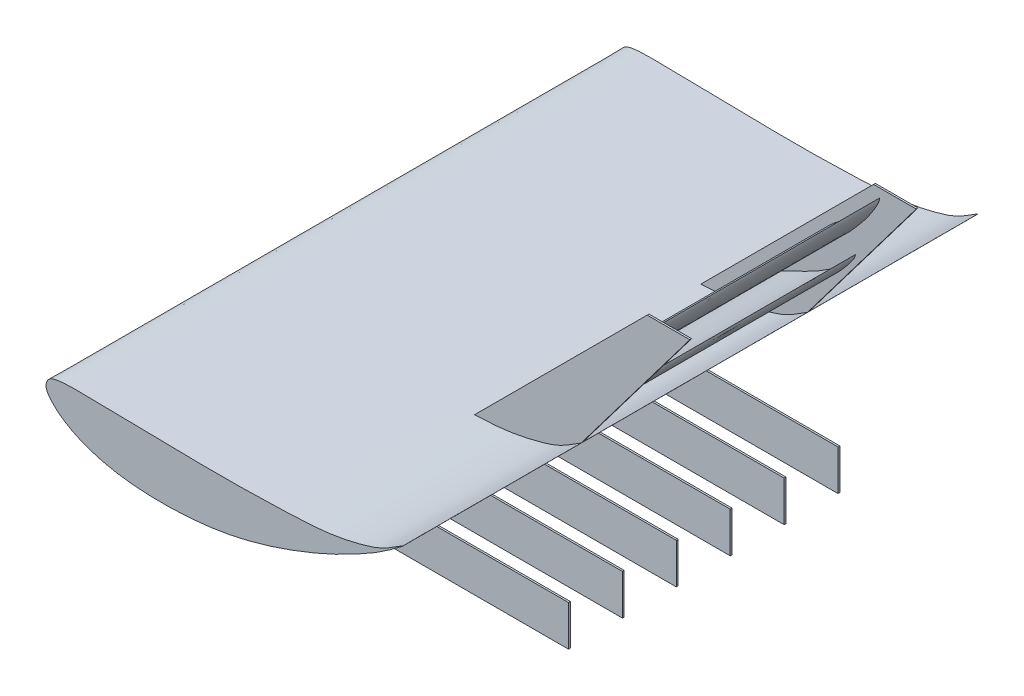
SolidWorks part; units mm, degrees
ref_plane "Front Plane" through (0, 0, 0) normal (0, 0, 1) x (1, 0, 0)
ref_plane "Top Plane" through (0, 0, 0) normal (0, 1, 0) x (1, 0, 0)
ref_plane "Right Plane" through (0, 0, 0) normal (1, 0, 0) x (0, 0, -1)
sketch "Sketch1" plane through (0, 0, 0) normal (0, 0, 1) x (1, 0, 0)
  line L0 (0, 0) -> (100, 0) construction
  line L1 (1.25, 16.6531) -> (1.25, -38.4553) construction
  line L2 (2.5, 17.9055) -> (2.5, -38.4614) construction
  line L3 (0, 16.6233) -> (0, -25.6938) construction
  line L4 (2.5, -38.4553) -> (2.5, 17.9055) construction
  line L6 (5, 17.9055) -> (5, -38.4553) construction
  line L8 (7.5, -38.4553) -> (7.5, 17.9055) construction
  line L10 (10, 17.9055) -> (10, -38.4553) construction
  line L12 (15, -38.4553) -> (15, 17.9055) construction
  line L14 (20, 17.9055) -> (20, -38.4553) construction
  line L16 (30, -38.4553) -> (30, 17.9055) construction
  line L18 (40, 17.9055) -> (40, -38.4553) construction
  line L20 (50, -38.4553) -> (50, 17.9055) construction
  line L22 (60, 17.9055) -> (60, -38.4553) construction
  line L24 (70, -38.4553) -> (70, 17.9055) construction
  line L26 (80, 17.9055) -> (80, -38.4553) construction
  line L28 (90, -38.4553) -> (90, 17.9055) construction
  line L30 (95, 17.9055) -> (95, -38.4553) construction
  line L32 (100, -38.4553) -> (100, 17.9055) construction
  spline S2 degree 3 poles (94.3673, -3.5638) (102.8561, 1.5222) (94.504, -2.988) (88.8138, -4.3065) (79.9056, -5.4947) (70.0198, -5.0741) (59.9849, -4.387) (49.9902, -3.5342) (39.9927, -2.4103) (30.0039, -1.1606) (21.6652, -0.2167) (14.9997, 0.5924) (10.0103, 1.184) (5.8366, 1.6528) (2.898, 1.5692) (0.8648, 1.1108) (-0.6238, -1.2668) (0.9385, -3.7627) (2.7533, -5.9838) (4.8768, -7.8493) (7.4255, -9.5789) (10.7358, -11.3943) (14.9019, -13.1207) (21.5668, -15.0457) (29.9416, -16.4142) (39.9918, -17.0298) (50.051, -16.6825) (60.0771, -15.2123) (70.1301, -12.7919) (80.007, -9.774) (88.8716, -6.1499) (94.3673, -3.5638) (102.8561, 1.5222) (94.504, -2.988) knots -0.105257 -0.054131 -0.027635 0 0.026268 0.051016 0.098804 0.146246 0.193788 0.241403 0.289125 0.336907 0.384666 0.408554 0.432437 0.456234 0.468112 0.474323 0.485191 0.50162 0.510955 0.52691 0.541278 0.554823 0.580548 0.60527 0.653411 0.700937 0.748406 0.796324 0.845052 0.894743 0.945869 0.972365 1 1.026268 1.051016 1.098804 only from (100, -0.1) to (100, -0.1)
  point P37 (0, -0.86)
  point P38 (1.25, -4.09)
  point P40 (1.25, 1.06)
  point P41 (2.5, 1.45)
  point P42 (5, -7.86)
  point P43 (2.5, -5.61)
  point P44 (5, 1.59)
  point P45 (7.5, -9.57)
  point P46 (7.5, 1.44)
  point P47 (10, 1.18)
  point P48 (15, 0.59)
  point P49 (15, -13.05)
  point P50 (20, -0.01)
  point P51 (20, -14.52)
  point P52 (30, -1.18)
  point P53 (30, -16.25)
  point P54 (40, -2.39)
  point P55 (10, -10.95)
  point P56 (40, -16.87)
  point P57 (40, -2.39)
  point P58 (50, -3.49)
  point P59 (50, -16.5)
  point P60 (60, -4.36)
  point P61 (60, -15.07)
  point P62 (70, -5.03)
  point P63 (70, -12.72)
  point P64 (80, -5.19)
  point P65 (80, -9.6)
  point P66 (90, -3.97)
  point P67 (90, -5.58)
  point P68 (95, -2.48)
  point P69 (95, -3.09)
  point P70 (100, -0.1)
  point P71 (100, -0.2)
  dimension "D1" = 100
  dimension "D2" = 1.25
  dimension "D3" = 2.5
  dimension "D4" = 2.5
  dimension "D5" = 7.5
  dimension "D6" = 10
  dimension "D7" = 15
  dimension "D8" = 5
  dimension "D9" = 10
  dimension "D10" = 10
  dimension "D11" = 10
  dimension "D12" = 10
  dimension "D13" = 10
  dimension "D14" = 10
  dimension "D15" = 10
  dimension "D16" = 5
  dimension "D17" = 5
curve "Curve1"
  spline degree 3 poles (98.5502, -0.8292, 0) (100.5299, 0.3794, 0) (99.1462, -0.6768, 0) (98.4443, -1.2755, 0) (97.3097, -2.0642, 0) (96.0009, -2.7117, 0) (94.4298, -3.3947, 0) (92.569, -4.0837, 0) (90.4012, -4.8122, 0) (87.9505, -5.5478, 0) (85.2749, -6.304, 0) (82.4359, -7.0338, 0) (79.5022, -7.7406, 0) (76.5208, -8.4057, 0) (73.5219, -9.0393, 0) (70.5175, -9.6161, 0) (67.5077, -10.1489, 0) (64.4881, -10.6321, 0) (61.4395, -11.0484, 0) (58.3521, -11.4274, 0) (55.2125, -11.781, 0) (52.0112, -12.0861, 0) (48.7533, -12.37, 0) (45.4544, -12.6663, 0) (42.1402, -12.9291, 0) (38.8572, -13.1898, 0) (35.6511, -13.4329, 0) (32.5711, -13.6325, 0) (29.6613, -13.7858, 0) (26.9506, -13.8772, 0) (24.4353, -13.8571, 0) (22.088, -13.7476, 0) (19.8826, -13.5013, 0) (17.7867, -13.168, 0) (15.7934, -12.7056, 0) (13.8906, -12.1349, 0) (12.076, -11.4655, 0) (10.3558, -10.6964, 0) (8.7488, -9.8421, 0) (7.2684, -8.933, 0) (5.9416, -8.0004, 0) (4.7755, -7.0863, 0) (3.7847, -6.217, 0) (2.957, -5.4094, 0) (2.269, -4.6735, 0) (1.728, -3.9816, 0) (1.2751, -3.3596, 0) (0.9309, -2.7719, 0) (0.6318, -2.2442, 0) (0.4105, -1.7465, 0) (0.2408, -1.2843, 0) (0.1068, -0.8552, 0) (0.0223, -0.45, 0) (-0.004, -0.0672, 0) (-0.0039, 0.3013, 0) (0.0809, 0.6622, 0) (0.2952, 0.9824, 0) (0.6315, 1.1995, 0) (1.032, 1.3336, 0) (1.4872, 1.4186, 0) (2.0055, 1.4764, 0) (2.6028, 1.5163, 0) (3.3032, 1.5313, 0) (4.1367, 1.5461, 0) (5.1573, 1.5223, 0) (6.4269, 1.4548, 0) (8.0274, 1.3654, 0) (10.0021, 1.2291, 0) (12.3384, 1.004, 0) (14.971, 0.7256, 0) (17.8195, 0.3367, 0) (20.844, -0.1077, 0) (24.0032, -0.6376, 0) (27.2668, -1.1722, 0) (30.5738, -1.7172, 0) (33.8785, -2.2723, 0) (37.1527, -2.7975, 0) (40.3807, -3.3138, 0) (43.5644, -3.7828, 0) (46.6972, -4.2145, 0) (49.7874, -4.5959, 0) (52.8339, -4.9281, 0) (55.8477, -5.1987, 0) (58.8316, -5.4085, 0) (61.7919, -5.5626, 0) (64.7329, -5.6385, 0) (67.6568, -5.6622, 0) (70.5644, -5.6128, 0) (73.4581, -5.4881, 0) (76.3366, -5.3163, 0) (79.1931, -5.05, 0) (82.0171, -4.7312, 0) (84.7804, -4.3625, 0) (87.434, -3.9036, 0) (89.9332, -3.4404, 0) (92.2075, -2.9247, 0) (94.233, -2.3848, 0) (95.9446, -1.8589, 0) (97.5056, -1.2357, 0) (98.5502, -0.8292, 0) (100.5299, 0.3794, 0) (99.1462, -0.6768, 0) knots -0.020778 -0.013318 -0.006872 0 0.003934 0.00967 0.015849 0.022782 0.030794 0.040273 0.051195 0.063508 0.076888 0.09098 0.105453 0.12007 0.134692 0.149314 0.163846 0.178433 0.193072 0.207875 0.222946 0.238282 0.253894 0.269743 0.28568 0.30147 0.316872 0.331691 0.345638 0.35857 0.370496 0.381625 0.392182 0.402235 0.411978 0.42144 0.430647 0.439636 0.448385 0.456672 0.46448 0.47158 0.477867 0.483331 0.488125 0.492267 0.495894 0.499125 0.502007 0.504569 0.506909 0.509051 0.510997 0.512815 0.514533 0.516257 0.518043 0.519896 0.521872 0.524061 0.526511 0.529332 0.532624 0.536536 0.54126 0.547229 0.554731 0.564199 0.575553 0.588316 0.602079 0.616691 0.632061 0.647918 0.664017 0.680023 0.695872 0.71147 0.726804 0.741922 0.756725 0.771359 0.785775 0.800025 0.814163 0.828192 0.842121 0.856004 0.869802 0.883566 0.897265 0.910851 0.924235 0.937151 0.949387 0.960589 0.970563 0.979222 0.986682 0.993128 1 1.003934 1.00967 1.015849 periodic
sketch "Sketch2" plane through (0, 0, 0) normal (0, 0, 1) x (1, 0, 0)
  line L0 (331.6325, -0.1558) -> (-65.7962, -45.4371) construction
  line L1 (-65.7962, -45.4371) -> (-68.337, -23.1365) construction
  line L2 (0, 0) -> (60.5483, 0) construction
  line L3 (385.2571, 82.501) -> (286.9589, 13.6718) construction
  line L4 (286.9589, 13.6718) -> (272.478, 34.3526) construction
  line L5 (331.6325, -0.1558) -> (331.6325, 76.9311) construction
  line L6 (331.6325, -0.1558) -> (397.2706, -0.1558) construction
  line L7 (412.1546, 150.4845) -> (355.5861, 93.9159) construction
  line L8 (299.294, 9.8442) -> (308.8152, 9.8442) construction
  line L9 (286.6325, 14.5606) -> (286.6325, 26.1748) construction
  line L10 (355.5861, 93.9159) -> (325.5679, 123.9341) construction
  line L11 (385.2571, 82.501) -> (439.2948, 82.501) construction
  line L12 (385.2571, 82.501) -> (385.2571, 253.7541) construction
  line L14 (360.5365, 92.501) -> (347.2815, 92.501) construction
  line L15 (355.2571, 94.5953) -> (355.2571, 86.9128) construction
  spline S1 degree 3 poles (384.8846, 81.2478) (385.5164, 83.2388) (384.4039, 80.6874) (383.6577, 79.5684) (382.5534, 77.8807) (381.234, 76.1849) (379.6159, 74.2589) (377.7366, 72.1854) (375.6004, 70.0085) (373.3094, 67.7296) (370.8484, 65.4636) (368.2936, 63.2048) (365.6704, 60.9752) (362.9606, 58.8233) (360.2036, 56.7073) (357.3809, 54.6556) (354.4918, 52.6644) (351.55, 50.7129) (348.5353, 48.8248) (345.4591, 46.9752) (342.3116, 45.1647) (339.0895, 43.3924) (335.7907, 41.6382) (332.4153, 39.904) (328.9642, 38.1714) (325.437, 36.4548) (321.8583, 34.7152) (318.229, 32.9837) (314.6045, 31.2409) (311.0296, 29.5177) (307.5607, 27.8619) (304.283, 26.2148) (301.2163, 24.6344) (298.438, 23.0944) (295.9876, 21.7059) (293.9535, 20.4794) (292.3194, 19.4647) (291.0255, 18.6563) (290.0064, 17.9765) (289.1977, 17.3878) (288.5198, 16.8905) (287.9605, 16.4397) (287.4911, 16.026) (287.1025, 15.6288) (286.8013, 15.2211) (286.6204, 14.7762) (286.6306, 14.3139) (286.7959, 13.9009) (287.0496, 13.5387) (287.3391, 13.1808) (287.7014, 12.8408) (288.1286, 12.5116) (288.6138, 12.1745) (289.1741, 11.8379) (289.8315, 11.5255) (290.5746, 11.1852) (291.4481, 10.8861) (292.4563, 10.579) (293.6392, 10.33) (295.0088, 10.1068) (296.5811, 9.9353) (298.3566, 9.8405) (300.3027, 9.8384) (302.3835, 9.9651) (304.5509, 10.2329) (306.7709, 10.6623) (309.0149, 11.2548) (311.2776, 12.005) (313.5546, 12.9239) (315.8434, 14.0403) (318.1798, 15.3178) (320.5616, 16.8273) (323.0467, 18.5404) (325.647, 20.4977) (328.4002, 22.653) (331.2889, 24.971) (334.2713, 27.4186) (337.3173, 29.9365) (340.3924, 32.4781) (343.4295, 35.0419) (346.4347, 37.5652) (349.3698, 40.0706) (352.2108, 42.5809) (354.9831, 45.0803) (357.6916, 47.5896) (360.3254, 50.1446) (362.9155, 52.7417) (365.4699, 55.3783) (367.9798, 58.0668) (370.4509, 60.7742) (372.8463, 63.4898) (375.1328, 66.1627) (377.2406, 68.7489) (379.1415, 71.1601) (380.7696, 73.3693) (382.1232, 75.3282) (383.1961, 77.0817) (384.0359, 78.6195) (384.6074, 80.1761) (384.8846, 81.2478) (385.5164, 83.2388) (384.4039, 80.6874) knots -0.015849 -0.00967 -0.003934 0 0.006872 0.013318 0.020778 0.029437 0.039411 0.050613 0.062849 0.075765 0.089149 0.102735 0.116434 0.130198 0.143996 0.157879 0.171808 0.185837 0.199975 0.214225 0.228641 0.243275 0.258078 0.273196 0.28853 0.304128 0.319977 0.335983 0.352082 0.367939 0.383309 0.397921 0.411684 0.424447 0.435801 0.445269 0.452771 0.45874 0.463464 0.467376 0.470668 0.473489 0.475939 0.478128 0.480104 0.481957 0.483743 0.485467 0.487185 0.489003 0.490949 0.493091 0.495431 0.497993 0.500875 0.504106 0.507733 0.511875 0.516669 0.522133 0.52842 0.53552 0.543328 0.551615 0.560364 0.569353 0.57856 0.588022 0.597765 0.607818 0.618375 0.629504 0.64143 0.654362 0.668309 0.683128 0.69853 0.71432 0.730257 0.746106 0.761718 0.777054 0.792125 0.806928 0.821567 0.836154 0.850686 0.865308 0.87993 0.894547 0.90902 0.923112 0.936492 0.948805 0.959727 0.969206 0.977218 0.984151 0.99033 0.996066 1 1.006872 1.013318 1.020778 only from (385.2571, 82.501) to (385.2571, 82.501)
  spline S2 degree 3 poles (310.6391, -16.2329) (342.3319, 7.4626) (310.948, -13.8864) (288.8507, -21.4531) (253.8988, -29.8144) (214.402, -32.1744) (174.2032, -33.5355) (134.0967, -34.2209) (93.8685, -33.8291) (53.6236, -32.9335) (20.0676, -32.5806) (-6.7778, -32.082) (-26.867, -31.764) (-43.661, -31.6021) (-55.3165, -33.1337) (-63.2173, -35.7866) (-68.169, -45.8522) (-60.9356, -55.1433) (-52.8102, -63.238) (-43.602, -69.7925) (-32.7577, -75.633) (-18.8487, -81.5041) (-1.572, -86.6718) (25.7261, -91.6102) (59.5991, -93.6371) (99.8297, -91.9854) (139.7029, -86.4995) (178.9865, -76.5608) (217.9897, -62.8307) (256.0482, -46.7957) (289.8325, -28.7623) (310.6391, -16.2329) (342.3319, 7.4626) (310.948, -13.8864) knots -0.105257 -0.054131 -0.027635 0 0.026268 0.051016 0.098804 0.146246 0.193788 0.241403 0.289125 0.336907 0.384666 0.408554 0.432437 0.456234 0.468112 0.474323 0.485191 0.50162 0.510955 0.52691 0.541278 0.554823 0.580548 0.60527 0.653411 0.700937 0.748406 0.796324 0.845052 0.894743 0.945869 0.972365 1 1.026268 1.051016 1.098804 only from (331.6325, -0.1558) to (331.6325, -0.1558)
  spline S3 degree 3 poles (412.0551, 149.6186) (412.2394, 150.9988) (411.8044, 149.195) (411.444, 148.3739) (410.9144, 147.1381) (410.2444, 145.8719) (409.4051, 144.4202) (408.4113, 142.8413) (407.2608, 141.1648) (406.0205, 139.4033) (404.6671, 137.6307) (403.2512, 135.852) (401.7872, 134.0845) (400.2572, 132.358) (398.692, 130.6496) (397.0763, 128.9757) (395.41, 127.334) (393.7045, 125.7123) (391.9439, 124.1236) (390.1384, 122.5532) (388.2815, 121.0002) (386.3712, 119.4635) (384.4085, 117.9299) (382.3932, 116.4006) (380.328, 114.8636) (378.211, 113.3282) (376.0628, 111.7718) (373.8805, 110.2149) (371.7026, 108.6511) (369.5551, 107.1059) (367.4692, 105.6172) (365.508, 104.1564) (363.6776, 102.7638) (362.0318, 101.4311) (360.5837, 100.2358) (359.3903, 99.1951) (358.4349, 98.3397) (357.6789, 97.6592) (357.0886, 97.0949) (356.6258, 96.6148) (356.2383, 96.2098) (355.9233, 95.8491) (355.663, 95.5231) (355.4538, 95.2174) (355.3033, 94.9148) (355.236, 94.6018) (355.2962, 94.2995) (355.4525, 94.0475) (355.6611, 93.839) (355.8926, 93.6376) (356.1697, 93.4563) (356.4883, 93.2896) (356.846, 93.1244) (357.2528, 92.9683) (357.7205, 92.8393) (358.2478, 92.7019) (358.8559, 92.6067) (359.5534, 92.5218) (360.3589, 92.4952) (361.2839, 92.5073) (362.336, 92.5766) (363.5127, 92.72) (364.7906, 92.9439) (366.142, 93.2679) (367.534, 93.6947) (368.9418, 94.2336) (370.3465, 94.8823) (371.7452, 95.6368) (373.1338, 96.5037) (374.5072, 97.5017) (375.8933, 98.6108) (377.2822, 99.8777) (378.7155, 101.29) (380.1961, 102.8761) (381.7542, 104.6099) (383.3824, 106.4662) (385.0571, 108.4184) (386.7654, 110.4241) (388.4901, 112.4487) (390.1873, 114.4835) (391.8682, 116.4881) (393.5052, 118.4728) (395.0798, 120.4498) (396.6106, 122.4116) (398.0983, 124.3726) (399.5317, 126.355) (400.9316, 128.3599) (402.3034, 130.3867) (403.6401, 132.4423) (404.949, 134.5059) (406.2072, 136.5661) (407.399, 138.5857) (408.4835, 140.5277) (409.4524, 142.3307) (410.2655, 143.9697) (410.9274, 145.4124) (411.4289, 146.6879) (411.8022, 147.7947) (411.9972, 148.8829) (412.0551, 149.6186) (412.2394, 150.9988) (411.8044, 149.195) knots -0.015849 -0.00967 -0.003934 0 0.006872 0.013318 0.020778 0.029437 0.039411 0.050613 0.062849 0.075765 0.089149 0.102735 0.116434 0.130198 0.143996 0.157879 0.171808 0.185837 0.199975 0.214225 0.228641 0.243275 0.258078 0.273196 0.28853 0.304128 0.319977 0.335983 0.352082 0.367939 0.383309 0.397921 0.411684 0.424447 0.435801 0.445269 0.452771 0.45874 0.463464 0.467376 0.470668 0.473489 0.475939 0.478128 0.480104 0.481957 0.483743 0.485467 0.487185 0.489003 0.490949 0.493091 0.495431 0.497993 0.500875 0.504106 0.507733 0.511875 0.516669 0.522133 0.52842 0.53552 0.543328 0.551615 0.560364 0.569353 0.57856 0.588022 0.597765 0.607818 0.618375 0.629504 0.64143 0.654362 0.668309 0.683128 0.69853 0.71432 0.730257 0.746106 0.761718 0.777054 0.792125 0.806928 0.821567 0.836154 0.850686 0.865308 0.87993 0.894547 0.90902 0.923112 0.936492 0.948805 0.959727 0.969206 0.977218 0.984151 0.99033 0.996066 1 1.006872 1.013318 1.020778 only from (412.1546, 150.4845) to (412.1546, 150.4845)
  dimension "D2" = 400
  dimension "D1" = 90
  dimension "D3" = 6.5
  dimension "D4" = 90
  dimension "D5" = 120
  dimension "D6" = 35
  dimension "D7" = 10
  dimension "D8" = 45
  dimension "D9" = 90
  dimension "D10" = 80
  dimension "D11" = 45
  dimension "D12" = 30
  dimension "D13" = 10
extrude "Boss-Extrude1" add sketch "Sketch2" along normal blind 450 and the other way blind 190 contours S2
extrude "Boss-Extrude2" add sketch "Sketch2<3>" along normal blind 250 separate body contours S1
sketch "Sketch2<3>" plane through (0, 0, 0) normal (0, 0, 1) x (1, 0, 0) same geometry as "Sketch2"
extrude "Boss-Extrude3" add sketch "Sketch2<4>" along normal blind 250 separate body contours S3
sketch "Sketch2<4>" plane through (0, 0, 0) normal (0, 0, 1) x (1, 0, 0) same geometry as "Sketch2"
sketch "Sketch3" plane through (0, 0, 0) normal (0, 0, 1) x (1, 0, 0)
  line L0 (213.126, -32.0618) -> (405.3691, 160.1813)
  line L1 (405.3691, 160.1813) -> (452.8645, 160.1813)
  line L2 (452.8645, 160.1813) -> (331.6325, -0.1558)
  spline S0 degree 3 poles (310.6391, -16.2329) (342.3319, 7.4626) (310.948, -13.8864) (288.8507, -21.4531) (253.8988, -29.8144) (214.402, -32.1744) (174.2032, -33.5355) (134.0967, -34.2209) (93.8685, -33.8291) (53.6236, -32.9335) (20.0676, -32.5806) (-6.7778, -32.082) (-26.867, -31.764) (-43.661, -31.6021) (-55.3165, -33.1337) (-63.2173, -35.7866) (-68.169, -45.8522) (-60.9356, -55.1433) (-52.8102, -63.238) (-43.602, -69.7925) (-32.7577, -75.633) (-18.8487, -81.5041) (-1.572, -86.6718) (25.7261, -91.6102) (59.5991, -93.6371) (99.8297, -91.9854) (139.7029, -86.4995) (178.9865, -76.5608) (217.9897, -62.8307) (256.0482, -46.7957) (289.8325, -28.7623) (310.6391, -16.2329) (342.3319, 7.4626) (310.948, -13.8864) knots -0.105257 -0.054131 -0.027635 0 0.026268 0.051016 0.098804 0.146246 0.193788 0.241403 0.289125 0.336907 0.384666 0.408554 0.432437 0.456234 0.468112 0.474323 0.485191 0.50162 0.510955 0.52691 0.541278 0.554823 0.580548 0.60527 0.653411 0.700937 0.748406 0.796324 0.845052 0.894743 0.945869 0.972365 1 1.026268 1.051016 1.098804 only from (331.6325, -0.1558) to (331.6325, -0.1558) construction
  spline S1 degree 3 poles (331.6325, -0.1558) (331.3048, -0.0386) (310.948, -13.8864) (288.8507, -21.4531) (253.8988, -29.8144) (227.165, -31.4118) (213.5191, -32.0438) (213.126, -32.0618) knots 0 0 0 0 0.026268 0.051016 0.098804 0.146246 0.147653 0.147653 0.147653 0.147653
extrude "Boss-Extrude4" add sketch "Sketch3" against normal blind 2
ref_plane "Plane1" through (0, 0, 125) normal (0, 0, 1) x (1, 0, 0)
mirror "Mirror1" about plane through (0, 0, 125) normal (0, 0, 1) of "Boss-Extrude4"
ref_plane "Plane2" through (0, 0, 185) normal (0, 0, 1) x (1, 0, 0)
ref_plane "Plane3" through (0, 0, 65) normal (0, 0, 1) x (1, 0, 0)
sketch "Sketch4" plane through (0, 0, 65) normal (0, 0, 1) x (1, 0, 0)
  line L0 (78.3177, -92.7012) -> (430.8358, -92.7012)
  line L1 (430.8358, -92.7012) -> (430.8358, -47.7012)
  line L2 (430.8358, -47.7012) -> (252.5788, -47.7012)
  spline S0 degree 3 poles (310.6391, -16.2329) (342.3319, 7.4626) (310.948, -13.8864) (288.8507, -21.4531) (253.8988, -29.8144) (214.402, -32.1744) (174.2032, -33.5355) (134.0967, -34.2209) (93.8685, -33.8291) (53.6236, -32.9335) (20.0676, -32.5806) (-6.7778, -32.082) (-26.867, -31.764) (-43.661, -31.6021) (-55.3165, -33.1337) (-63.2173, -35.7866) (-68.169, -45.8522) (-60.9356, -55.1433) (-52.8102, -63.238) (-43.602, -69.7925) (-32.7577, -75.633) (-18.8487, -81.5041) (-1.572, -86.6718) (25.7261, -91.6102) (59.5991, -93.6371) (99.8297, -91.9854) (139.7029, -86.4995) (178.9865, -76.5608) (217.9897, -62.8307) (256.0482, -46.7957) (289.8325, -28.7623) (310.6391, -16.2329) (342.3319, 7.4626) (310.948, -13.8864) knots -0.105257 -0.054131 -0.027635 0 0.026268 0.051016 0.098804 0.146246 0.193788 0.241403 0.289125 0.336907 0.384666 0.408554 0.432437 0.456234 0.468112 0.474323 0.485191 0.50162 0.510955 0.52691 0.541278 0.554823 0.580548 0.60527 0.653411 0.700937 0.748406 0.796324 0.845052 0.894743 0.945869 0.972365 1 1.026268 1.051016 1.098804 only from (331.6325, -0.1558) to (331.6325, -0.1558) construction
  spline S1 degree 3 poles (78.3177, -92.7012) (85.4873, -92.437) (105.9683, -91.1408) (139.7029, -86.4995) (178.9865, -76.5608) (216.8353, -63.237) (240.8302, -53.2039) (252.5788, -47.7012) knots 0.675413 0.675413 0.675413 0.675413 0.700937 0.748406 0.796324 0.845052 0.890412 0.890412 0.890412 0.890412
  dimension "D1" = 45
  dimension "D2" = 45
extrude "Boss-Extrude5" add sketch "Sketch4" against normal blind 2
pattern_linear "LPattern1" count 6 spacing 60 along (0, 0, 1) of "Boss-Extrude5"
ref_plane "Plane4" through (0, 0, -190) normal (0, 0, 1) x (1, 0, 0)
